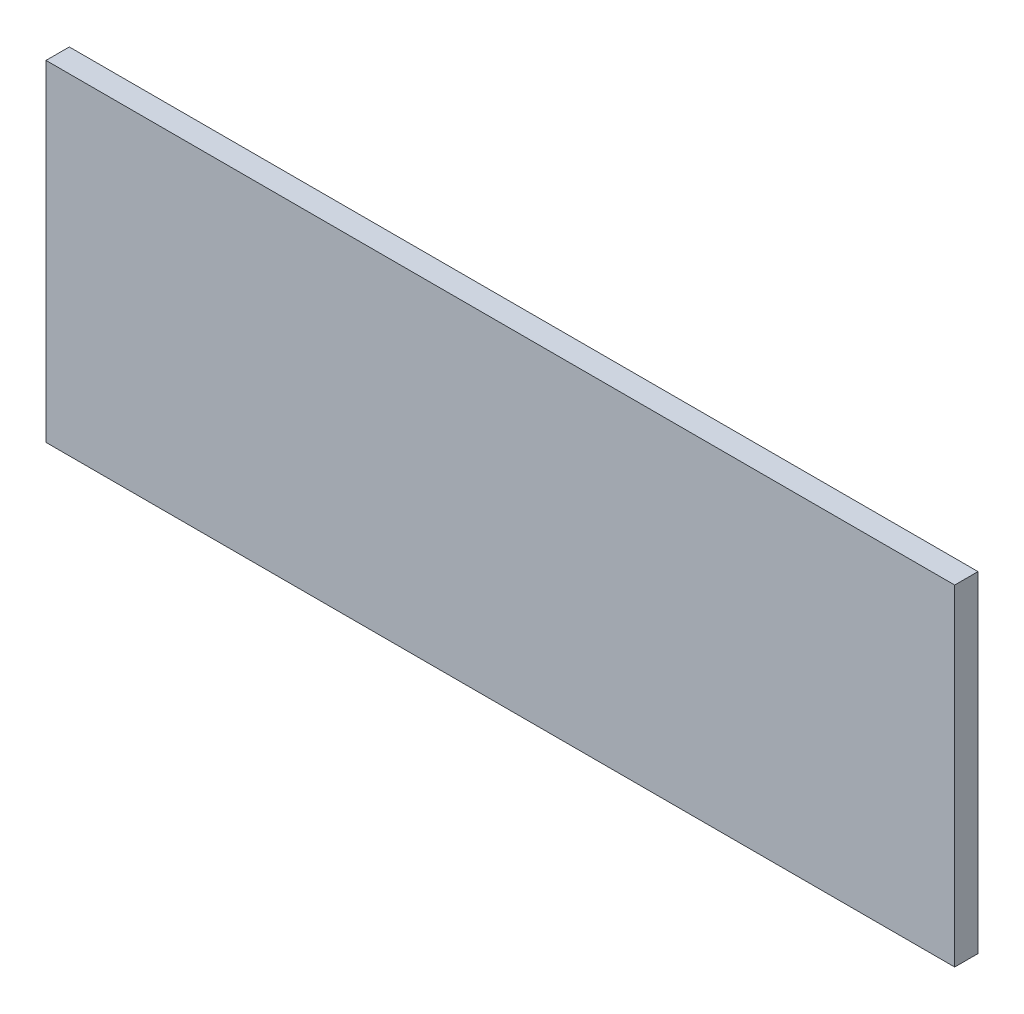
SolidWorks part; units mm, degrees
ref_plane "Front Plane" through (0, 0, 0) normal (0, 0, 1) x (1, 0, 0)
ref_plane "Top Plane" through (0, 0, 0) normal (0, 1, 0) x (1, 0, 0)
ref_plane "Right Plane" through (0, 0, 0) normal (1, 0, 0) x (0, 0, -1)
sketch "Sketch1" plane through (0, 0, 0) normal (0, 0, 1) x (1, 0, 0)
  line L1 (195, -71) -> (-195, -71)
  line L2 (195, -71) -> (195, 71)
  line L3 (195, 71) -> (-195, 71)
  line L4 (-195, -71) -> (-195, 71)
  line L5 (195, -71) -> (-195, 71) construction
  line L6 (195, 71) -> (-195, -71) construction
  point P0 (0, 0)
  dimension "D1" = 390
  dimension "D2" = 142
extrude "Boss-Extrude1" add sketch "Sketch1" along normal mid plane 10
